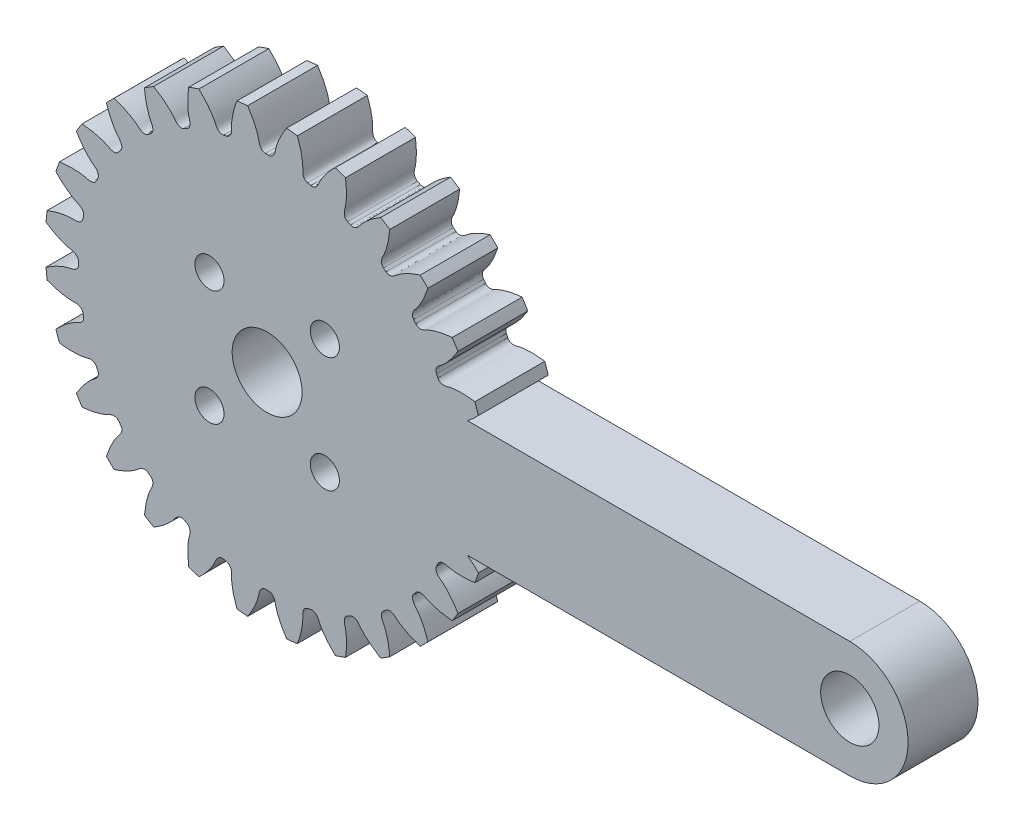
SolidWorks part; units mm, degrees
material "2014 合金"
ref_plane "Front Plane" through (0, 0, 0) normal (0, 0, 1) x (1, 0, 0)
ref_plane "Top Plane" through (0, 0, 0) normal (0, 1, 0) x (1, 0, 0)
ref_plane "Right Plane" through (0, 0, 0) normal (1, 0, 0) x (0, 0, -1)
ref_axis "Axis1" through (0, 0, -8.6927) along (0, 0, 1)
sketch "Gear-BaseSketch" plane through (0, 0, 0) normal (0, 0, 1) x (1, 0, 0)
  circle A0 centre (0, 0) radius 19.05
  dimension "D1" = 38.1
extrude "20.0 Diametral Pitch, 35.5600mm P.D." add sketch "Gear-BaseSketch" along normal mid plane 6
sketch "Tooth-Sketch; Backlash: 0.0000mm" plane through (0, 0, 0) normal (0, 0, 1) x (1, 0, 0)
  line L0 (0, 0) -> (0, 25.0616) construction
  arc A0 (-1.7329, 19.0679) -> (1.7329, 19.0679) centre (0, 0) cw
  arc A1 (-0.1392, 16.1919) -> (0.1392, 16.1919) centre (0, 0) cw
  spline S0 degree 3 poles (-1.7329, 19.0679) (-1.6101, 18.8888) (-1.4415, 18.6236) (-1.2453, 18.2714) (-1.1239, 18.033) (-1.0212, 17.8114) (-0.9358, 17.6075) (-0.8662, 17.4224) (-0.811, 17.2569) (-0.7684, 17.1118) (-0.7371, 16.9878) (-0.7172, 16.8956) (-0.7058, 16.832) (-0.6981, 16.7904) (-0.6901, 16.7533) (-0.6758, 16.6938) (-0.6515, 16.6133) (-0.6099, 16.5133) (-0.5534, 16.4157) (-0.4723, 16.3196) (-0.3383, 16.2221) (-0.214, 16.1923) (-0.1392, 16.1919) knots 0 0 0 0 0.191018 0.276294 0.354748 0.42638 0.49119 0.549178 0.600343 0.644687 0.682208 0.712908 0.727669 0.739016 0.750139 0.761058 0.792861 0.824038 0.856152 0.891705 0.934026 1 1 1 1
  spline S1 degree 3 poles (1.7329, 19.0679) (1.6101, 18.8888) (1.4415, 18.6236) (1.2453, 18.2714) (1.1239, 18.033) (1.0212, 17.8114) (0.9358, 17.6075) (0.8662, 17.4224) (0.811, 17.2569) (0.7684, 17.1118) (0.7371, 16.9878) (0.7172, 16.8956) (0.7058, 16.832) (0.6981, 16.7904) (0.6901, 16.7533) (0.6758, 16.6938) (0.6515, 16.6133) (0.6099, 16.5133) (0.5534, 16.4157) (0.4723, 16.3196) (0.3383, 16.2221) (0.214, 16.1923) (0.1392, 16.1919) knots 0 0 0 0 0.191018 0.276294 0.354748 0.42638 0.49119 0.549178 0.600343 0.644687 0.682208 0.712908 0.727669 0.739016 0.750139 0.761058 0.792861 0.824038 0.856152 0.891705 0.934026 1 1 1 1
extrude "Tooth-Cut, Coarse Pitch Involute 20 deg" cut sketch "Tooth-Sketch; Backlash: 0.0000mm" against normal through all and the other way through all
pattern_circular "Tooth Pattern, 28 / 28" count 28 every 12.857 about axis through (0, 0, -8.6927) along (0, 0, 1) of "Tooth-Cut, Coarse Pitch Involute 20 deg"
sketch "Sketch3" plane through (0, 0, 3) normal (0, 0, 1) x (1, 0, 0)
  circle A0 centre (0, 0) radius 14 construction
  circle A1 centre (0, 0) radius 5
  dimension "D1" = 28
  dimension "D2" = 10
extrude "Cut-Extrude2" cut sketch "Sketch3" against normal blind 2
mirror "Mirror1" [suppressed] about plane through (0, 0, 0) normal (0, 0, 1)
sketch "Sketch4" plane through (0, 0, 3) normal (0, 0, 1) x (1, 0, 0)
  circle A0 centre (0, 0) radius 3
  dimension "D1" = 6
extrude "Cut-Extrude3" cut sketch "Sketch4" against normal through all
sketch "Sketch5" plane through (0, 0, 0) normal (0, 0, 1) x (1, 0, 0)
  line L0 (0, 0) -> (50, 0) construction
  line L1 (0, 5) -> (50, 5)
  line L2 (0, -5) -> (50, -5)
  arc A0 (0, 5) -> (0, -5) centre (0, 0) ccw
  arc A1 (50, -5) -> (50, 5) centre (50, 0) ccw
  circle A2 centre (0, 0) radius 3
  circle A3 centre (50, 0) radius 2.5
  circle A5 centre (0, 0) radius 5 construction
  point P3 (25, 0)
  dimension "D2" = 5
  dimension "D3" = 6
  dimension "D1" = 50
extrude "Boss-Extrude2" add sketch "Sketch5" along normal mid plane 6
hole_wizard "M3 螺纹孔1" positions "草图2" profile "草图1" tap size "M3" standard "Gb"
sketch "草图2" plane through (0, 0, 3) normal (0, 0, 1) x (1, 0, 0)
  line L0 (0, 0) -> (-6.2664, -6.2664) construction
  line L3 (0, 0) -> (-10.1066, 0) construction
  circle A0 centre (0, 0) radius 7 construction
  point P0 (-4.9497, -4.9497)
  dimension "D1" = 14
  dimension "D2" = 45
sketch "草图1" plane through (-4.9497, -4.9497, 3) normal (1, 0, 0) x (0, -1, 0)
  line L0 (0, 0) -> (0, 9.2511)
  line L1 (0, 9.2511) -> (1.25, 8.5)
  line L2 (1.25, 8.5) -> (1.25, 0)
  line L5 (1.25, 0) -> (0, 0)
  line L10 (0, 9.2511) -> (-1.25, 8.5) construction
  line L11 (0, -6.35) -> (0, 107.95) construction
  dimension "螺纹孔钻头直径" = 2.5
  dimension "螺纹孔钻头深度" = 8.5
  dimension "导头角度" = 118
cosmetic thread "孔螺蚊线1" parameters "D1"=6, "D2"=3
pattern_circular "阵列(圆周)1" count 4 over 360 about axis through (0, 0, -3) along (0, 0, 1) of "M3 螺纹孔1"
